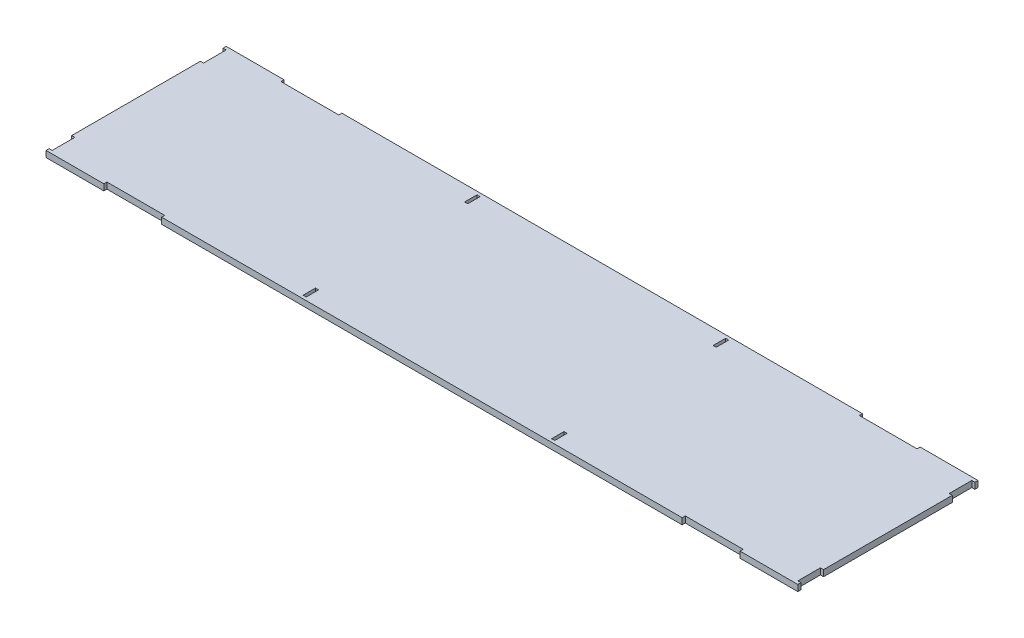
SolidWorks part; units mm, degrees
ref_plane "Front Plane" through (0, 0, 0) normal (0, 0, 1) x (1, 0, 0)
ref_plane "Top Plane" through (0, 0, 0) normal (0, 1, 0) x (1, 0, 0)
ref_plane "Right Plane" through (0, 0, 0) normal (1, 0, 0) x (0, 0, -1)
sketch "Sketch1" plane through (0, 0, 0) normal (0, 1, 0) x (1, 0, 0)
  line L0 (0, 88.9) -> (0, -88.9) construction
  line L1 (-381, 88.9) -> (381, 88.9)
  line L2 (-381, 88.9) -> (-381, -88.9)
  line L3 (-381, -88.9) -> (381, -88.9)
  line L4 (381, 88.9) -> (381, -88.9)
  line L5 (-381, 39.4607) -> (-381, 65.7679)
  line L6 (-381, 65.7679) -> (-384.175, 65.7679)
  line L7 (-381, 65.7679) -> (-381, 92.075)
  line L8 (-381, 92.075) -> (-384.175, 92.075)
  line L9 (-384.175, 65.7679) -> (-384.175, 92.075)
  line L14 (-325.0712, -88.9) -> (-384.175, -88.9)
  line L15 (-325.0712, -88.9) -> (-325.0712, -92.075)
  line L16 (-325.0712, -92.075) -> (-384.175, -92.075)
  line L17 (-384.175, -88.9) -> (-384.175, -92.075)
  line L18 (381, 65.7679) -> (384.175, 65.7679)
  line L19 (381, 65.7679) -> (381, 92.075)
  line L20 (381, 92.075) -> (384.175, 92.075)
  line L21 (384.175, 65.7679) -> (384.175, 92.075)
  line L22 (-325.0712, 88.9) -> (-384.175, 88.9)
  line L23 (-325.0712, 88.9) -> (-325.0712, 92.075)
  line L24 (-325.0712, 92.075) -> (-384.175, 92.075)
  line L25 (-384.175, 88.9) -> (-384.175, 92.075)
  line L26 (-381, 39.4607) -> (-384.175, 39.4607)
  line L27 (-384.175, 39.4607) -> (-384.175, 65.7679)
  line L28 (-381, 65.7679) -> (-384.175, 65.7679)
  line L29 (381, 39.4607) -> (381, 65.7679)
  line L30 (381, 39.4607) -> (384.175, 39.4607)
  line L31 (384.175, 39.4607) -> (384.175, 65.7679)
  line L32 (381, 65.7679) -> (384.175, 65.7679)
  line L33 (-381, 13.1536) -> (-381, 39.4607)
  line L34 (-381, 13.1536) -> (-384.175, 13.1536)
  line L35 (-384.175, 13.1536) -> (-384.175, 39.4607)
  line L36 (-381, 39.4607) -> (-384.175, 39.4607)
  line L37 (381, 13.1536) -> (381, 39.4607)
  line L38 (381, 13.1536) -> (384.175, 13.1536)
  line L39 (384.175, 13.1536) -> (384.175, 39.4607)
  line L40 (381, 39.4607) -> (384.175, 39.4607)
  line L41 (-381, -13.1536) -> (-381, 13.1536)
  line L42 (-381, -13.1536) -> (-384.175, -13.1536)
  line L43 (-384.175, -13.1536) -> (-384.175, 13.1536)
  line L44 (-381, 13.1536) -> (-384.175, 13.1536)
  line L45 (381, -13.1536) -> (381, 13.1536)
  line L46 (381, -13.1536) -> (384.175, -13.1536)
  line L47 (384.175, -13.1536) -> (384.175, 13.1536)
  line L48 (381, 13.1536) -> (384.175, 13.1536)
  line L49 (-381, -39.4607) -> (-381, -13.1536)
  line L50 (-381, -39.4607) -> (-384.175, -39.4607)
  line L51 (-384.175, -39.4607) -> (-384.175, -13.1536)
  line L52 (-381, -13.1536) -> (-384.175, -13.1536)
  line L53 (381, -39.4607) -> (381, -13.1536)
  line L54 (381, -39.4607) -> (384.175, -39.4607)
  line L55 (384.175, -39.4607) -> (384.175, -13.1536)
  line L56 (381, -13.1536) -> (384.175, -13.1536)
  line L57 (-381, -65.7679) -> (-381, -39.4607)
  line L58 (-381, -65.7679) -> (-384.175, -65.7679)
  line L59 (-384.175, -65.7679) -> (-384.175, -39.4607)
  line L60 (-381, -39.4607) -> (-384.175, -39.4607)
  line L61 (381, -65.7679) -> (381, -39.4607)
  line L62 (381, -65.7679) -> (384.175, -65.7679)
  line L63 (384.175, -65.7679) -> (384.175, -39.4607)
  line L64 (381, -39.4607) -> (384.175, -39.4607)
  line L65 (-381, -92.075) -> (-381, -65.7679)
  line L66 (-381, -92.075) -> (-384.175, -92.075)
  line L67 (-384.175, -92.075) -> (-384.175, -65.7679)
  line L68 (-381, -65.7679) -> (-384.175, -65.7679)
  line L69 (381, -92.075) -> (381, -65.7679)
  line L70 (381, -92.075) -> (384.175, -92.075)
  line L71 (384.175, -92.075) -> (384.175, -65.7679)
  line L72 (381, -65.7679) -> (384.175, -65.7679)
  line L73 (-265.9673, -88.9) -> (-265.9673, -92.075)
  line L74 (-265.9673, -88.9) -> (-325.0712, -88.9)
  line L75 (-325.0712, -88.9) -> (-325.0712, -92.075)
  line L76 (-265.9673, -92.075) -> (-325.0712, -92.075)
  line L77 (-265.9673, 88.9) -> (-265.9673, 92.075)
  line L78 (-265.9673, 88.9) -> (-325.0712, 88.9)
  line L79 (-325.0712, 88.9) -> (-325.0712, 92.075)
  line L80 (-265.9673, 92.075) -> (-325.0712, 92.075)
  line L81 (-206.8635, -88.9) -> (-206.8635, -92.075)
  line L82 (-206.8635, -88.9) -> (-265.9673, -88.9)
  line L83 (-265.9673, -88.9) -> (-265.9673, -92.075)
  line L84 (-206.8635, -92.075) -> (-265.9673, -92.075)
  line L85 (-206.8635, 88.9) -> (-206.8635, 92.075)
  line L86 (-206.8635, 88.9) -> (-265.9673, 88.9)
  line L87 (-265.9673, 88.9) -> (-265.9673, 92.075)
  line L88 (-206.8635, 92.075) -> (-265.9673, 92.075)
  line L89 (-147.7596, -88.9) -> (-147.7596, -92.075)
  line L90 (-147.7596, -88.9) -> (-206.8635, -88.9)
  line L91 (-206.8635, -88.9) -> (-206.8635, -92.075)
  line L92 (-147.7596, -92.075) -> (-206.8635, -92.075)
  line L93 (-147.7596, 88.9) -> (-147.7596, 92.075)
  line L94 (-147.7596, 88.9) -> (-206.8635, 88.9)
  line L95 (-206.8635, 88.9) -> (-206.8635, 92.075)
  line L96 (-147.7596, 92.075) -> (-206.8635, 92.075)
  line L97 (-88.6558, -88.9) -> (-88.6558, -92.075)
  line L98 (-88.6558, -88.9) -> (-147.7596, -88.9)
  line L99 (-147.7596, -88.9) -> (-147.7596, -92.075)
  line L100 (-88.6558, -92.075) -> (-147.7596, -92.075)
  line L101 (-88.6558, 88.9) -> (-88.6558, 92.075)
  line L102 (-88.6558, 88.9) -> (-147.7596, 88.9)
  line L103 (-147.7596, 88.9) -> (-147.7596, 92.075)
  line L104 (-88.6558, 92.075) -> (-147.7596, 92.075)
  line L105 (-29.5519, -88.9) -> (-29.5519, -92.075)
  line L106 (-29.5519, -88.9) -> (-88.6558, -88.9)
  line L107 (-88.6558, -88.9) -> (-88.6558, -92.075)
  line L108 (-29.5519, -92.075) -> (-88.6558, -92.075)
  line L109 (-29.5519, 88.9) -> (-29.5519, 92.075)
  line L110 (-29.5519, 88.9) -> (-88.6558, 88.9)
  line L111 (-88.6558, 88.9) -> (-88.6558, 92.075)
  line L112 (-29.5519, 92.075) -> (-88.6558, 92.075)
  line L113 (29.5519, -88.9) -> (29.5519, -92.075)
  line L114 (29.5519, -88.9) -> (-29.5519, -88.9)
  line L115 (-29.5519, -88.9) -> (-29.5519, -92.075)
  line L116 (29.5519, -92.075) -> (-29.5519, -92.075)
  line L117 (29.5519, 88.9) -> (29.5519, 92.075)
  line L118 (29.5519, 88.9) -> (-29.5519, 88.9)
  line L119 (-29.5519, 88.9) -> (-29.5519, 92.075)
  line L120 (29.5519, 92.075) -> (-29.5519, 92.075)
  line L121 (88.6558, -88.9) -> (88.6558, -92.075)
  line L122 (88.6558, -88.9) -> (29.5519, -88.9)
  line L123 (29.5519, -88.9) -> (29.5519, -92.075)
  line L124 (88.6558, -92.075) -> (29.5519, -92.075)
  line L125 (88.6558, 88.9) -> (88.6558, 92.075)
  line L126 (88.6558, 88.9) -> (29.5519, 88.9)
  line L127 (29.5519, 88.9) -> (29.5519, 92.075)
  line L128 (88.6558, 92.075) -> (29.5519, 92.075)
  line L129 (147.7596, -88.9) -> (147.7596, -92.075)
  line L130 (147.7596, -88.9) -> (88.6558, -88.9)
  line L131 (88.6558, -88.9) -> (88.6558, -92.075)
  line L132 (147.7596, -92.075) -> (88.6558, -92.075)
  line L133 (147.7596, 88.9) -> (147.7596, 92.075)
  line L134 (147.7596, 88.9) -> (88.6558, 88.9)
  line L135 (88.6558, 88.9) -> (88.6558, 92.075)
  line L136 (147.7596, 92.075) -> (88.6558, 92.075)
  line L137 (206.8635, -88.9) -> (206.8635, -92.075)
  line L138 (206.8635, -88.9) -> (147.7596, -88.9)
  line L139 (147.7596, -88.9) -> (147.7596, -92.075)
  line L140 (206.8635, -92.075) -> (147.7596, -92.075)
  line L141 (206.8635, 88.9) -> (206.8635, 92.075)
  line L142 (206.8635, 88.9) -> (147.7596, 88.9)
  line L143 (147.7596, 88.9) -> (147.7596, 92.075)
  line L144 (206.8635, 92.075) -> (147.7596, 92.075)
  line L145 (265.9673, -88.9) -> (265.9673, -92.075)
  line L146 (265.9673, -88.9) -> (206.8635, -88.9)
  line L147 (206.8635, -88.9) -> (206.8635, -92.075)
  line L148 (265.9673, -92.075) -> (206.8635, -92.075)
  line L149 (265.9673, 88.9) -> (265.9673, 92.075)
  line L150 (265.9673, 88.9) -> (206.8635, 88.9)
  line L151 (206.8635, 88.9) -> (206.8635, 92.075)
  line L152 (265.9673, 92.075) -> (206.8635, 92.075)
  line L185 (325.0712, -88.9) -> (325.0712, -92.075)
  line L186 (325.0712, -88.9) -> (265.9673, -88.9)
  line L187 (265.9673, -88.9) -> (265.9673, -92.075)
  line L188 (325.0712, -92.075) -> (265.9673, -92.075)
  line L189 (325.0712, 88.9) -> (325.0712, 92.075)
  line L190 (325.0712, 88.9) -> (265.9673, 88.9)
  line L191 (265.9673, 88.9) -> (265.9673, 92.075)
  line L192 (325.0712, 92.075) -> (265.9673, 92.075)
  line L193 (384.175, -88.9) -> (384.175, -92.075)
  line L194 (384.175, -88.9) -> (325.0712, -88.9)
  line L195 (325.0712, -88.9) -> (325.0712, -92.075)
  line L196 (384.175, -92.075) -> (325.0712, -92.075)
  line L197 (384.175, 88.9) -> (384.175, 92.075)
  line L198 (384.175, 88.9) -> (325.0712, 88.9)
  line L199 (325.0712, 88.9) -> (325.0712, 92.075)
  line L200 (384.175, 92.075) -> (325.0712, 92.075)
  point P8 (0, 88.9)
  point P9 (0, 0)
  dimension "D1" = 762
  dimension "D2" = 177.8
  dimension "D3" = 184.15
  dimension "D5" = 768.35
  dimension "D6" = 26.3071
  dimension "D8" = 59.1038
  dimension "D4" = 7
  dimension "D7" = 13
extrude "Boss-Extrude1" add sketch "Sketch1" along normal blind 6.35 contours L0 L1 L2 L3 | L126 L0 L122 L3 L4 L1 | L65 L16 L15 L3 | L16 L65 L14 L17 | L84 L81 L3 L73 | L59 L58 L2 L50 | L100 L97 L3 L89 | L43 L42 L2 L34 | L27 L26 L2 L6 | L22 L7 L8 L9 | L23 L24 L7 L1 | L85 L88 L77 L1 | L101 L104 L93 L1 | L117 L120 L109 L1 | L133 L136 L125 L1 | L116 L113 L3 L105 | L132 L129 L3 L121 | L148 L145 L3 L137 | L149 L152 L141 L1 | L21 L20 L19 | L30 L31 L18 L4 | L46 L47 L38 L4 | L62 L63 L54 L4 | L71 L69 L70 | L193 L196 L195 L194 | L197 L200 L199 L198 region at (190.5, 0, 0) region at (-190.5, 0, 0) region at (0, 0, -90.4875) region at (0, 0, 90.4875) region at (-118.2077, 0, -90.4875) region at (118.2077, 0, -90.4875) region at (-118.2077, 0, 90.4875) region at (118.2077, 0, 90.4875) region at (-236.4154, 0, -90.4875) region at (236.4154, 0, -90.4875) region at (-236.4154, 0, 90.4875) region at (236.4154, 0, 90.4875) region at (-353.0356, 0, -90.4875) region at (-353.0356, 0, 90.4875) region at (-382.5875, 0, -90.4875) region at (382.5875, 0, -90.4875) region at (-382.5875, 0, 90.4875) region at (382.5875, 0, 90.4875) region at (-382.5875, 0, -52.6143) region at (382.5875, 0, -52.6143) region at (-382.5875, 0, 52.6143) region at (382.5875, 0, 52.6143) region at (-382.5875, 0, 0) region at (382.5875, 0, 0)
sketch "Sketch2" plane through (0, 6.35, 0) normal (0, 1, 0) x (1, 0, 0)
  line L0 (-125.4125, 0) -> (125.4125, 0) construction
  line L1 (-128.5875, 15.4404) -> (-125.4125, 15.4404) construction
  line L2 (-128.5875, 15.4404) -> (-128.5875, -15.4404) construction
  line L3 (-128.5875, -15.4404) -> (-125.4125, -15.4404) construction
  line L4 (-125.4125, 15.4404) -> (-125.4125, -15.4404) construction
  line L5 (125.4125, 14.3164) -> (128.5875, 14.3164) construction
  line L6 (125.4125, 14.3164) -> (125.4125, -14.3164) construction
  line L7 (125.4125, -14.3164) -> (128.5875, -14.3164) construction
  line L8 (128.5875, 14.3164) -> (128.5875, -14.3164) construction
  line L9 (-129.3813, 24.6215) -> (-124.6188, 24.6215) construction
  line L10 (-127, 24.6215) -> (-127, 15.4404) construction
  line L12 (-124.6188, 76.2) -> (-121.4438, 76.2)
  line L13 (-124.6188, 76.2) -> (-124.6188, 88.9)
  line L14 (-124.6188, 88.9) -> (-121.4438, 88.9)
  line L15 (-121.4438, 76.2) -> (-121.4438, 88.9)
  line L16 (-124.6188, 24.6215) -> (-124.6188, 76.2) construction
  line L18 (-121.4438, -88.9) -> (-124.6188, -88.9)
  line L19 (-121.4438, -88.9) -> (-121.4438, -76.2)
  line L20 (-121.4438, -76.2) -> (-124.6188, -76.2)
  line L21 (-124.6188, -88.9) -> (-124.6188, -76.2)
  line L31 (-206.8635, 88.9) -> (-147.7596, 88.9) construction
  line L32 (-206.8635, -88.9) -> (-147.7596, -88.9) construction
  line L33 (129.3813, 76.2) -> (129.3812, 88.9)
  line L34 (129.3813, 76.2) -> (132.5562, 76.2)
  line L35 (132.5562, 76.2) -> (132.5562, 88.9)
  line L36 (129.3812, 88.9) -> (132.5562, 88.9)
  line L37 (132.5562, -88.9) -> (132.5562, -76.2)
  line L38 (132.5562, -88.9) -> (129.3812, -88.9)
  line L39 (129.3812, -88.9) -> (129.3812, -76.2)
  line L40 (132.5562, -76.2) -> (129.3812, -76.2)
  line L41 (124.6188, 24.6215) -> (129.3813, 24.6215) construction
  line L42 (127, 24.6215) -> (127, 14.3164) construction
  line L43 (129.3813, 24.6215) -> (129.3813, 76.2) construction
  point P10 (0, 0)
  point P43 (127, 14.3164)
  dimension "D1" = 3.175
  dimension "D2" = 4.7625
  dimension "D4" = 3.175
  dimension "D5" = 12.7
  dimension "D3" = 254
  dimension "D6" = 2
extrude "Cut-Extrude1" cut sketch "Sketch2" against normal through all
sketch "Sketch3" plane through (0, 6.35, 0) normal (0, 1, 0) x (1, 0, 0)
  line L1 (-206.8635, -92.075) -> (-147.7596, -92.075)
  line L2 (-206.8635, -92.075) -> (-206.8635, -88.9)
  line L3 (-206.8635, -88.9) -> (-147.7596, -88.9)
  line L4 (-147.7596, -92.075) -> (-147.7596, -88.9)
  line L5 (-88.6558, -92.075) -> (-29.5519, -92.075)
  line L6 (-88.6558, -92.075) -> (-88.6558, -88.9)
  line L7 (-88.6558, -88.9) -> (-29.5519, -88.9)
  line L8 (-29.5519, -92.075) -> (-29.5519, -88.9)
  line L9 (29.5519, -92.075) -> (88.6558, -92.075)
  line L10 (29.5519, -92.075) -> (29.5519, -88.9)
  line L11 (29.5519, -88.9) -> (88.6558, -88.9)
  line L12 (88.6558, -92.075) -> (88.6558, -88.9)
  line L13 (147.7596, -92.075) -> (206.8635, -92.075)
  line L14 (147.7596, -92.075) -> (147.7596, -88.9)
  line L15 (147.7596, -88.9) -> (206.8635, -88.9)
  line L16 (206.8635, -92.075) -> (206.8635, -88.9)
  line L17 (384.175, -39.4607) -> (381, -39.4607)
  line L18 (384.175, -39.4607) -> (384.175, -13.1536)
  line L19 (384.175, -13.1536) -> (381, -13.1536)
  line L20 (381, -39.4607) -> (381, -13.1536)
  line L21 (384.175, 13.1536) -> (381, 13.1536)
  line L22 (384.175, 13.1536) -> (384.175, 39.4607)
  line L23 (384.175, 39.4607) -> (381, 39.4607)
  line L24 (381, 13.1536) -> (381, 39.4607)
  line L25 (-384.175, -13.1536) -> (-381, -13.1536)
  line L26 (-384.175, -13.1536) -> (-384.175, -39.4607)
  line L27 (-384.175, -39.4607) -> (-381, -39.4607)
  line L28 (-381, -13.1536) -> (-381, -39.4607)
  line L29 (-384.175, 39.4607) -> (-381, 39.4607)
  line L30 (-384.175, 39.4607) -> (-384.175, 13.1536)
  line L31 (-384.175, 13.1536) -> (-381, 13.1536)
  line L32 (-381, 39.4607) -> (-381, 13.1536)
  line L33 (-206.8635, 88.9) -> (-147.7596, 88.9)
  line L34 (-206.8635, 88.9) -> (-206.8635, 92.075)
  line L35 (-206.8635, 92.075) -> (-147.7596, 92.075)
  line L36 (-147.7596, 88.9) -> (-147.7596, 92.075)
  line L37 (-88.6558, 88.9) -> (-29.5519, 88.9)
  line L38 (-88.6558, 88.9) -> (-88.6558, 92.075)
  line L39 (-88.6558, 92.075) -> (-29.5519, 92.075)
  line L40 (-29.5519, 88.9) -> (-29.5519, 92.075)
  line L41 (29.5519, 88.9) -> (88.6558, 88.9)
  line L42 (29.5519, 88.9) -> (29.5519, 92.075)
  line L43 (29.5519, 92.075) -> (88.6558, 92.075)
  line L44 (88.6558, 88.9) -> (88.6558, 92.075)
  line L45 (147.7596, 88.9) -> (206.8635, 88.9)
  line L46 (147.7596, 88.9) -> (147.7596, 92.075)
  line L47 (147.7596, 92.075) -> (206.8635, 92.075)
  line L48 (206.8635, 88.9) -> (206.8635, 92.075)
extrude "Boss-Extrude2" add sketch "Sketch3" against normal up to surface (6.35 mm away) up to face at (130.9687, 0, -82.55)
equation "\"Height\"= 12in"
equation "\"Depth\"= 7in"
equation "\"WallThickness\"= 0.125in"
equation "\"FloorThickness\"= 0.25in"
equation "\"D1@Sketch1\"=\"Width\""
equation "\"D2@Sketch1\"=\"Depth\""
equation "\"D3@Sketch1\"=\"D2@Sketch1\"+2*\"WallThickness\""
equation "\"D5@Sketch1\"=\"D1@Sketch1\"+2*\"WallThickness\""
equation "\"D6@Sketch1\"=\"D3@Sketch1\"/\"D4@Sketch1\""
equation "\"D8@Sketch1\"=\"D5@Sketch1\"/\"D7@Sketch1\""
equation "\"D1@Boss-Extrude1\"=\"FloorThickness\""
equation "\"D1@Sketch2\"=\"WallThickness\""
equation "\"D2@Sketch2\"=\"WallThickness\"+(1/16in)"
equation "\"D4@Sketch2\"=\"WallThickness\""
equation "\"Width\"= 30in"
